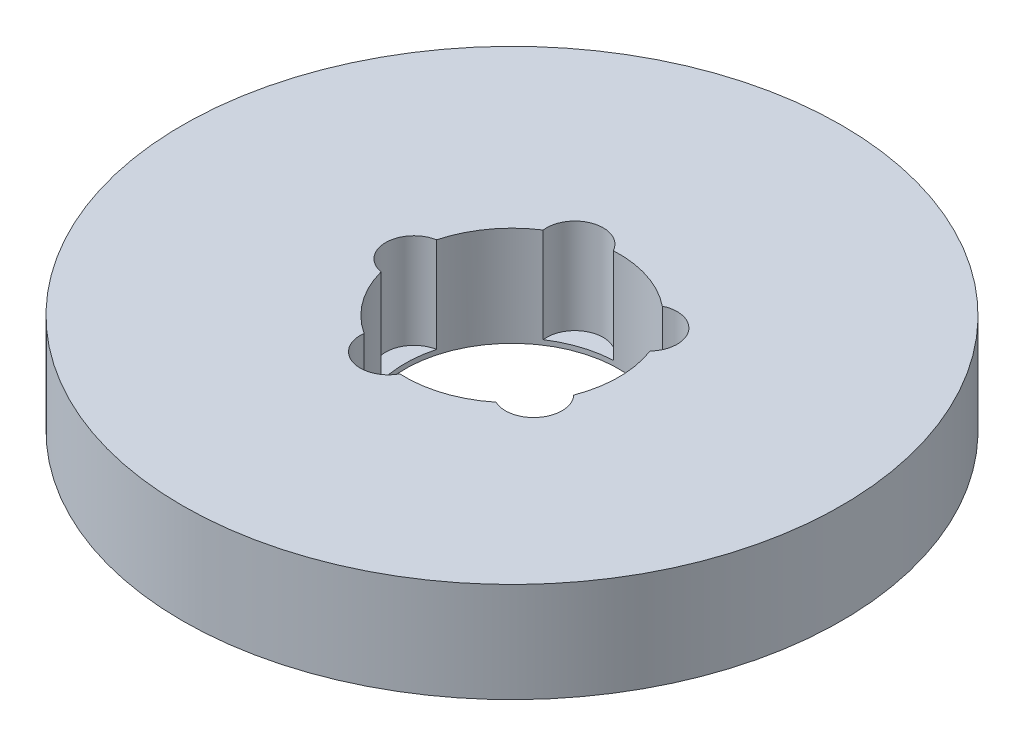
SolidWorks part; units mm, degrees
ref_plane "Front Plane" through (0, 0, 0) normal (0, 0, 1) x (1, 0, 0)
ref_plane "Top Plane" through (0, 0, 0) normal (0, 1, 0) x (1, 0, 0)
ref_plane "Right Plane" through (0, 0, 0) normal (1, 0, 0) x (0, 0, -1)
sketch "Sketch1" plane through (0, 0, 0) normal (0, 1, 0) x (1, 0, 0)
  circle A0 centre (0, 0) radius 92.5
  dimension "FLANGE_OD" = 185
extrude "Boss-Extrude1" add sketch "Sketch1" along normal blind 28
sketch "Sketch2" plane through (0, 0, 0) normal (0, 1, 0) x (1, 0, 0)
  circle A0 centre (0, 0) radius 30
  dimension "BORE_D" = 60
extrude "Cut-Extrude1" cut sketch "Sketch2" along normal through all
sketch "Sketch3" plane through (0, 28, 0) normal (0, 1, 0) x (1, 0, 0)
  circle A0 centre (0, 0) radius 27.5104 construction
  circle A1 centre (-27.5104, 0) radius 7.9423
  dimension "BOLT_D" = 15.8846
  dimension "BOLT_PCD" = 55.0208
extrude "Cut-Extrude2" cut sketch "Sketch3" against normal blind 26.648
pattern_circular "CirPattern1" count 5 over 360 about axis through (0, 0, 0) along (0, 1, 0) of "Cut-Extrude2"
